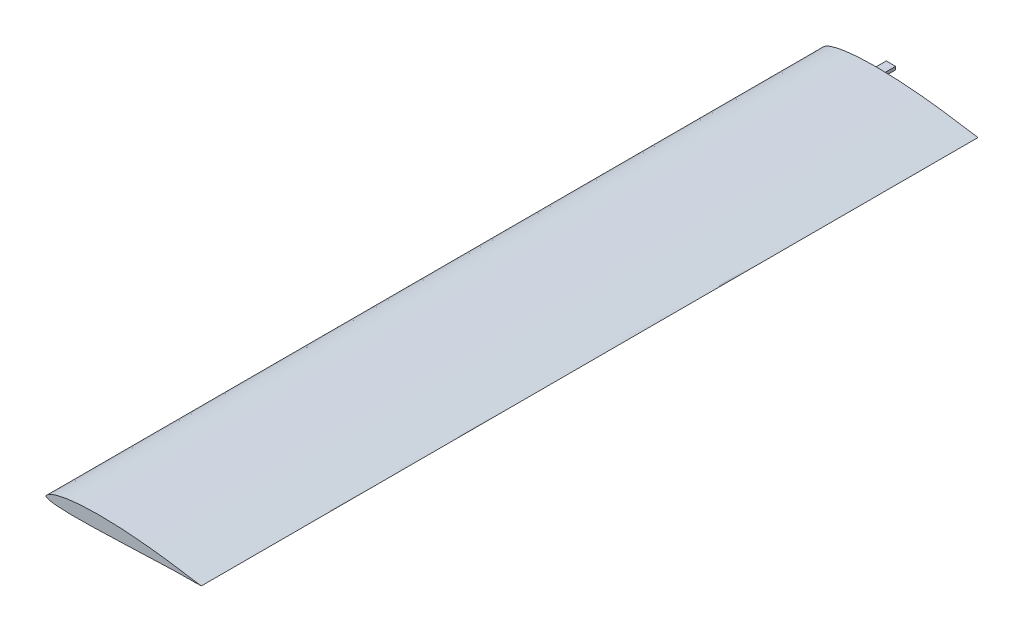
SolidWorks part; units mm, degrees
ref_plane "Front Plane" through (0, 0, 0) normal (0, 0, 1) x (1, 0, 0)
ref_plane "Top Plane" through (0, 0, 0) normal (0, 1, 0) x (1, 0, 0)
ref_plane "Right Plane" through (0, 0, 0) normal (1, 0, 0) x (0, 0, -1)
curve "Curve1"
  spline degree 3 poles (49.6515, 0.009, 0) (50.0884, -0.0053, 0) (49.6522, 0.033, 0) (49.3011, 0.0832, 0) (48.4593, 0.1945, 0) (47.4415, 0.3499, 0) (46.1338, 0.5549, 0) (44.6155, 0.7993, 0) (42.8923, 1.0751, 0) (40.9958, 1.371, 0) (38.9477, 1.6747, 0) (36.7703, 1.9711, 0) (34.4838, 2.2498, 0) (32.109, 2.5048, 0) (29.6686, 2.7322, 0) (27.1889, 2.9318, 0) (24.6971, 3.0996, 0) (22.2188, 3.2252, 0) (19.7784, 3.3048, 0) (17.3996, 3.3388, 0) (15.1043, 3.321, 0) (12.9138, 3.2492, 0) (10.8475, 3.1296, 0) (8.9245, 2.9596, 0) (7.1613, 2.7404, 0) (5.5715, 2.4767, 0) (4.1671, 2.1739, 0) (2.9576, 1.8376, 0) (1.9505, 1.4773, 0) (1.1488, 1.103, 0) (0.5587, 0.7311, 0) (0.2281, 0.4366, 0) (0.09, 0.2394, 0) (0.0408, 0.1522, 0) (0.0104, 0.0738, 0) (-0.0015, 0.012, 0) (0.0009, -0.0367, 0) (0.0247, -0.0804, 0) (0.0694, -0.1305, 0) (0.1411, -0.1885, 0) (0.3144, -0.2962, 0) (0.7005, -0.4536, 0) (1.3781, -0.6282, 0) (2.3375, -0.7877, 0) (3.539, -0.9182, 0) (4.9742, -1.0154, 0) (6.6312, -1.0793, 0) (8.4956, -1.1107, 0) (10.5497, -1.112, 0) (12.7728, -1.0868, 0) (15.1414, -1.0389, 0) (17.6298, -0.9723, 0) (20.2103, -0.8906, 0) (22.8538, -0.7976, 0) (25.5303, -0.6969, 0) (28.2091, -0.5925, 0) (30.859, -0.4876, 0) (33.449, -0.3866, 0) (35.9478, -0.2924, 0) (38.325, -0.208, 0) (40.551, -0.1358, 0) (42.5964, -0.0785, 0) (44.4361, -0.0365, 0) (46.0378, -0.0091, 0) (47.399, 0.0043, 0) (48.4441, 0.0096, 0) (49.2972, 0.0042, 0) (49.6515, 0.009, 0) (50.0884, -0.0053, 0) (49.6522, 0.033, 0) knots -0.014204 -0.006419 -0.001632 0 0.001631 0.006435 0.014221 0.024766 0.037827 0.053149 0.070474 0.089536 0.110075 0.13186 0.154693 0.178371 0.20268 0.227364 0.252133 0.276728 0.300939 0.324527 0.347267 0.368992 0.389507 0.408628 0.426224 0.442179 0.456396 0.468805 0.479372 0.488086 0.494968 0.500034 0.501036 0.502094 0.502997 0.503513 0.503956 0.504409 0.504955 0.505943 0.50713 0.510998 0.518232 0.527846 0.539809 0.554056 0.57049 0.588974 0.609342 0.631393 0.654894 0.67959 0.705203 0.731447 0.75802 0.78462 0.810936 0.836657 0.861473 0.885081 0.907188 0.927507 0.945765 0.961712 0.975122 0.985796 0.993581 0.998368 1 1.001631 1.006435 1.014221 periodic
sketch "Sketch1" plane through (0, 0, 0) normal (0, 0, 1) x (1, 0, 0)
  spline S0 degree 3 poles (49.6515, 0.009) (50.0884, -0.0053) (49.6522, 0.033) (49.3011, 0.0832) (48.4593, 0.1945) (47.4415, 0.3499) (46.1338, 0.5549) (44.6155, 0.7993) (42.8923, 1.0751) (40.9958, 1.371) (38.9477, 1.6747) (36.7703, 1.9711) (34.4838, 2.2498) (32.109, 2.5048) (29.6686, 2.7322) (27.1889, 2.9318) (24.6971, 3.0996) (22.2188, 3.2252) (19.7784, 3.3048) (17.3996, 3.3388) (15.1043, 3.321) (12.9138, 3.2492) (10.8475, 3.1296) (8.9245, 2.9596) (7.1613, 2.7404) (5.5715, 2.4767) (4.1671, 2.1739) (2.9576, 1.8376) (1.9505, 1.4773) (1.1488, 1.103) (0.5587, 0.7311) (0.2281, 0.4366) (0.09, 0.2394) (0.0408, 0.1522) (0.0104, 0.0738) (-0.0015, 0.012) (0.0009, -0.0367) (0.0247, -0.0804) (0.0694, -0.1305) (0.1411, -0.1885) (0.3144, -0.2962) (0.7005, -0.4536) (1.3781, -0.6282) (2.3375, -0.7877) (3.539, -0.9182) (4.9742, -1.0154) (6.6312, -1.0793) (8.4956, -1.1107) (10.5497, -1.112) (12.7728, -1.0868) (15.1414, -1.0389) (17.6298, -0.9723) (20.2103, -0.8906) (22.8538, -0.7976) (25.5303, -0.6969) (28.2091, -0.5925) (30.859, -0.4876) (33.449, -0.3866) (35.9478, -0.2924) (38.325, -0.208) (40.551, -0.1358) (42.5964, -0.0785) (44.4361, -0.0365) (46.0378, -0.0091) (47.399, 0.0043) (48.4441, 0.0096) (49.2972, 0.0042) (49.6515, 0.009) (50.0884, -0.0053) (49.6522, 0.033) knots -0.014204 -0.006419 -0.001632 0 0.001631 0.006435 0.014221 0.024766 0.037827 0.053149 0.070474 0.089536 0.110075 0.13186 0.154693 0.178371 0.20268 0.227364 0.252133 0.276728 0.300939 0.324527 0.347267 0.368992 0.389507 0.408628 0.426224 0.442179 0.456396 0.468805 0.479372 0.488086 0.494968 0.500034 0.501036 0.502094 0.502997 0.503513 0.503956 0.504409 0.504955 0.505943 0.50713 0.510998 0.518232 0.527846 0.539809 0.554056 0.57049 0.588974 0.609342 0.631393 0.654894 0.67959 0.705203 0.731447 0.75802 0.78462 0.810936 0.836657 0.861473 0.885081 0.907188 0.927507 0.945765 0.961712 0.975122 0.985796 0.993581 0.998368 1 1.001631 1.006435 1.014221 only from (50, 0) to (50, 0) construction
  spline S1 degree 3 poles (49.6515, 0.009) (50.0884, -0.0053) (49.6522, 0.033) (49.3011, 0.0832) (48.4593, 0.1945) (47.4415, 0.3499) (46.1338, 0.5549) (44.6155, 0.7993) (42.8923, 1.0751) (40.9958, 1.371) (38.9477, 1.6747) (36.7703, 1.9711) (34.4838, 2.2498) (32.109, 2.5048) (29.6686, 2.7322) (27.1889, 2.9318) (24.6971, 3.0996) (22.2188, 3.2252) (19.7784, 3.3048) (17.3996, 3.3388) (15.1043, 3.321) (12.9138, 3.2492) (10.8475, 3.1296) (8.9245, 2.9596) (7.1613, 2.7404) (5.5715, 2.4767) (4.1671, 2.1739) (2.9576, 1.8376) (1.9505, 1.4773) (1.1488, 1.103) (0.5587, 0.7311) (0.2281, 0.4366) (0.09, 0.2394) (0.0408, 0.1522) (0.0104, 0.0738) (-0.0015, 0.012) (0.0009, -0.0367) (0.0247, -0.0804) (0.0694, -0.1305) (0.1411, -0.1885) (0.3144, -0.2962) (0.7005, -0.4536) (1.3781, -0.6282) (2.3375, -0.7877) (3.539, -0.9182) (4.9742, -1.0154) (6.6312, -1.0793) (8.4956, -1.1107) (10.5497, -1.112) (12.7728, -1.0868) (15.1414, -1.0389) (17.6298, -0.9723) (20.2103, -0.8906) (22.8538, -0.7976) (25.5303, -0.6969) (28.2091, -0.5925) (30.859, -0.4876) (33.449, -0.3866) (35.9478, -0.2924) (38.325, -0.208) (40.551, -0.1358) (42.5964, -0.0785) (44.4361, -0.0365) (46.0378, -0.0091) (47.399, 0.0043) (48.4441, 0.0096) (49.2972, 0.0042) (49.6515, 0.009) (50.0884, -0.0053) (49.6522, 0.033) knots -0.014204 -0.006419 -0.001632 0 0.001631 0.006435 0.014221 0.024766 0.037827 0.053149 0.070474 0.089536 0.110075 0.13186 0.154693 0.178371 0.20268 0.227364 0.252133 0.276728 0.300939 0.324527 0.347267 0.368992 0.389507 0.408628 0.426224 0.442179 0.456396 0.468805 0.479372 0.488086 0.494968 0.500034 0.501036 0.502094 0.502997 0.503513 0.503956 0.504409 0.504955 0.505943 0.50713 0.510998 0.518232 0.527846 0.539809 0.554056 0.57049 0.588974 0.609342 0.631393 0.654894 0.67959 0.705203 0.731447 0.75802 0.78462 0.810936 0.836657 0.861473 0.885081 0.907188 0.927507 0.945765 0.961712 0.975122 0.985796 0.993581 0.998368 1 1.001631 1.006435 1.014221 only from (50, 0) to (50, 0)
extrude "Boss-Extrude1" add sketch "Sketch1" along normal blind 250
sketch "Sketch2" plane through (0, 0, 0) normal (0, 0, -1) x (-1, 0, 0)
  line L0 (0, 0) -> (-50, 0) construction
  line L2 (-18.473, 1.59) -> (-15.473, 1.59)
  line L3 (-18.473, 1.59) -> (-18.473, 0.59)
  line L4 (-18.473, 0.59) -> (-15.473, 0.59)
  line L5 (-15.473, 1.59) -> (-15.473, 0.59)
  line L6 (-18.473, 1.59) -> (-15.473, 0.59) construction
  line L7 (-18.473, 0.59) -> (-15.473, 1.59) construction
  spline S0 degree 3 poles (-49.6522, 0.033) (-50.0884, -0.0053) (-49.6515, 0.009) (-49.2972, 0.0042) (-48.4441, 0.0096) (-47.399, 0.0043) (-46.0378, -0.0091) (-44.4361, -0.0365) (-42.5964, -0.0785) (-40.551, -0.1358) (-38.325, -0.208) (-35.9478, -0.2924) (-33.449, -0.3866) (-30.859, -0.4876) (-28.2091, -0.5925) (-25.5303, -0.6969) (-22.8538, -0.7976) (-20.2103, -0.8906) (-17.6298, -0.9723) (-15.1414, -1.0389) (-12.7728, -1.0868) (-10.5497, -1.112) (-8.4956, -1.1107) (-6.6312, -1.0793) (-4.9742, -1.0154) (-3.539, -0.9182) (-2.3375, -0.7877) (-1.3781, -0.6282) (-0.7005, -0.4536) (-0.3144, -0.2962) (-0.1411, -0.1885) (-0.0694, -0.1305) (-0.0247, -0.0804) (-0.0009, -0.0367) (0.0015, 0.012) (-0.0104, 0.0738) (-0.0408, 0.1522) (-0.09, 0.2394) (-0.2281, 0.4366) (-0.5587, 0.7311) (-1.1488, 1.103) (-1.9505, 1.4773) (-2.9576, 1.8376) (-4.1671, 2.1739) (-5.5715, 2.4767) (-7.1613, 2.7404) (-8.9245, 2.9596) (-10.8475, 3.1296) (-12.9138, 3.2492) (-15.1043, 3.321) (-17.3996, 3.3388) (-19.7784, 3.3048) (-22.2188, 3.2252) (-24.6971, 3.0996) (-27.1889, 2.9318) (-29.6686, 2.7322) (-32.109, 2.5048) (-34.4838, 2.2498) (-36.7703, 1.9711) (-38.9477, 1.6747) (-40.9958, 1.371) (-42.8923, 1.0751) (-44.6155, 0.7993) (-46.1338, 0.5549) (-47.4415, 0.3499) (-48.4593, 0.1945) (-49.3011, 0.0832) (-49.6522, 0.033) (-50.0884, -0.0053) (-49.6515, 0.009) knots -0.014221 -0.006435 -0.001631 0 0.001632 0.006419 0.014204 0.024878 0.038288 0.054235 0.072493 0.092812 0.114919 0.138527 0.163343 0.189064 0.21538 0.24198 0.268553 0.294797 0.32041 0.345106 0.368607 0.390658 0.411026 0.42951 0.445944 0.460191 0.472154 0.481768 0.489002 0.49287 0.494057 0.495045 0.495591 0.496044 0.496487 0.497003 0.497906 0.498964 0.499966 0.505032 0.511914 0.520628 0.531195 0.543604 0.557821 0.573776 0.591372 0.610493 0.631008 0.652733 0.675473 0.699061 0.723272 0.747867 0.772636 0.79732 0.821629 0.845307 0.86814 0.889925 0.910464 0.929526 0.946851 0.962173 0.975234 0.985779 0.993565 0.998369 1 1.001632 1.006419 1.014204 only from (-50, 0) to (-50, 0) construction
  point P4 (-16.973, 1.09)
  dimension "D1" = 3
  dimension "D2" = 1
  dimension "D3" = 1.59
  dimension "D4" = 31.527
extrude "Boss-Extrude2" add sketch "Sketch2" along normal blind 5
